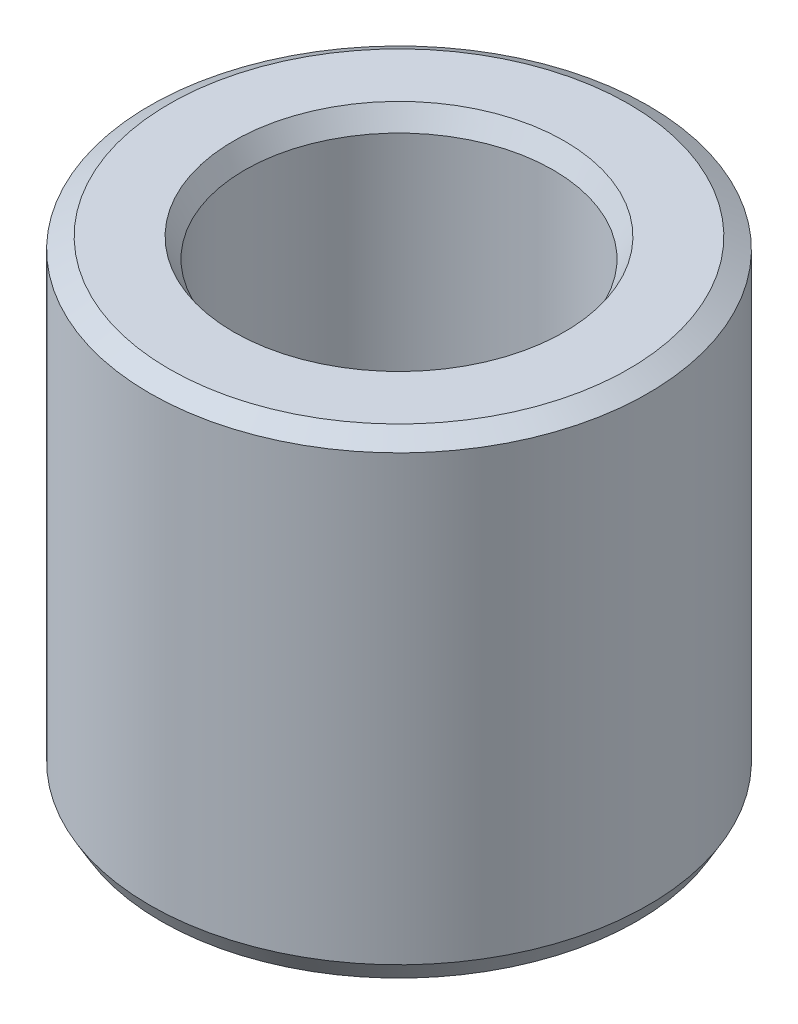
SolidWorks part; units mm, degrees
ref_plane "Front Plane" through (0, 0, 0) normal (0, 0, 1) x (1, 0, 0)
ref_plane "Top Plane" through (0, 0, 0) normal (0, 1, 0) x (1, 0, 0)
ref_plane "Right Plane" through (0, 0, 0) normal (1, 0, 0) x (0, 0, -1)
sketch "Sketch1" plane through (0, 0, 0) normal (0, 1, 0) x (1, 0, 0)
  circle A0 centre (0, 0) radius 32.5
  dimension "SLEEVE_OD" = 65
extrude "Boss-Extrude1" add sketch "Sketch1" along normal blind 61.8248
sketch "Sketch2" plane through (0, 0, 0) normal (0, 1, 0) x (1, 0, 0)
  circle A0 centre (0, 0) radius 20.1075
  dimension "BORE_D" = 40.2149
extrude "Cut-Extrude1" cut sketch "Sketch2" along normal through all
chamfer "Chamfer1" distance 1.467 angle 60 4 edges at (0, 61.8248, 20.1075) (0, 0, 20.1075) (0, 0, 32.5) (0, 61.8248, 32.5) first distance on face at (0, 61.8248, 20.1075) first distance on face at (0, 0, 20.1075) first distance on face at (0, 61.8248, 32.5)
